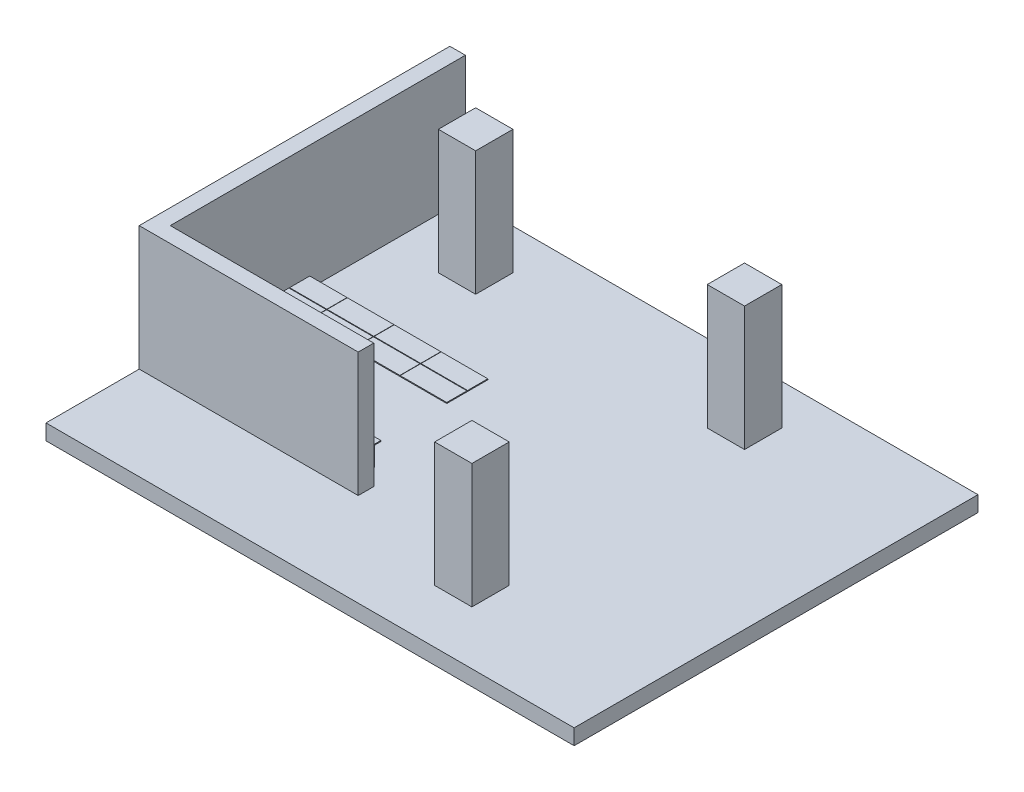
SolidWorks part; units mm, degrees
ref_plane "前视基准面" through (0, 0, 0) normal (0, 0, 1) x (1, 0, 0)
ref_plane "上视基准面" through (0, 0, 0) normal (0, 1, 0) x (1, 0, 0)
ref_plane "右视基准面" through (0, 0, 0) normal (1, 0, 0) x (0, 0, -1)
other "Configuration Table"
sketch "草图2" plane through (0, 0, 0) normal (0, 1, 0) x (1, 0, 0)
  line L5 (0, -500) -> (-500, -500)
  line L6 (0, -500) -> (0, 9500)
  line L7 (0, 9500) -> (-500, 9500)
  line L8 (-500, -500) -> (-500, 9500)
  line L9 (1630, 8200) -> (2830, 8200)
  line L10 (1630, 8200) -> (1630, 7000)
  line L11 (1630, 7000) -> (2830, 7000)
  line L12 (2830, 8200) -> (2830, 7000)
  line L13 (10285, 8200) -> (11485, 8200)
  line L14 (10285, 8200) -> (10285, 7000)
  line L15 (10285, 7000) -> (11485, 7000)
  line L16 (11485, 8200) -> (11485, 7000)
  line L17 (10285, -575) -> (11485, -575)
  line L18 (10285, -575) -> (10285, -1775)
  line L19 (10285, -1775) -> (11485, -1775)
  line L20 (11485, -575) -> (11485, -1775)
  line L21 (0, 0) -> (6550, 0)
  line L22 (0, 0) -> (0, -500)
  line L23 (0, -500) -> (6550, -500)
  line L24 (6550, 0) -> (6550, -500)
  point P4 (8000.3157, 0)
  dimension "D1" = 500
  dimension "D2" = 6550
  dimension "D3" = 500
  dimension "D4" = 10000
  dimension "D5" = 1200
  dimension "D6" = 1630
  dimension "D8" = 7455
  dimension "D9" = 7575
extrude "凸台-拉伸5" add sketch "草图2" along normal blind 4000 contours L6 L7 L8 L5 | L22 L21 L24 L23 | L11 L12 L9 L10 | L15 L16 L13 L14 | L19 L20 L17 L18
sketch "草图3" plane through (0, 0, 0) normal (0, 1, 0) x (1, 0, 0)
  line L1 (-500, 9500) -> (16500, 9500)
  line L2 (-500, 9500) -> (-500, -3500)
  line L3 (-500, -3500) -> (16500, -3500)
  line L4 (16500, 9500) -> (16500, -3500)
  dimension "D1" = 13000
  dimension "D2" = 17000
extrude "凸台-拉伸6" add sketch "草图3" against normal blind 500 contours L3 L4 L1 L2
sketch "草图4" plane through (0, 0, 0) normal (0, 1, 0) x (1, 0, 0)
  line L0 (0, 0) -> (6550, 0) construction
  line L1 (400, 650) -> (1600, 650)
  line L2 (400, 650) -> (400, 0)
  line L3 (400, 0) -> (1600, 0)
  line L4 (1600, 650) -> (1600, 0)
  line L5 (1610, 650) -> (3110, 650)
  line L6 (1610, 650) -> (1610, 0)
  line L7 (1610, 0) -> (3110, 0)
  line L8 (3110, 650) -> (3110, 0)
  line L9 (5905.4419, 3261.9478) -> (5805.4419, 3261.9478)
  line L14 (3120, 650) -> (4620, 650)
  line L19 (0, 0) -> (0, 9500) construction
  line L20 (3120, 650) -> (3120, 0)
  line L21 (3120, 0) -> (4620, 0)
  line L22 (4620, 650) -> (4620, 0)
  line L23 (4630, 650) -> (6130, 650)
  line L24 (4630, 650) -> (4630, 0)
  line L25 (4630, 0) -> (6130, 0)
  line L26 (6130, 650) -> (6130, 0)
  line L27 (1400, 550) -> (1500, 550)
  line L28 (500, 550) -> (600, 550)
  line L29 (500, 550) -> (500, 450)
  line L30 (500, 450) -> (600, 450)
  line L31 (600, 550) -> (600, 450)
  line L32 (500, 200) -> (600, 200)
  line L33 (500, 200) -> (500, 100)
  line L34 (500, 100) -> (600, 100)
  line L35 (600, 200) -> (600, 100)
  line L36 (1710, 550) -> (1810, 550)
  line L37 (1710, 550) -> (1710, 450)
  line L38 (1710, 450) -> (1810, 450)
  line L39 (1810, 550) -> (1810, 450)
  line L40 (1400, 200) -> (1500, 200)
  line L41 (1400, 200) -> (1400, 100)
  line L42 (1400, 100) -> (1500, 100)
  line L43 (1500, 200) -> (1500, 100)
  line L44 (1400, 550) -> (1400, 450)
  line L45 (1400, 450) -> (1500, 450)
  line L46 (1500, 550) -> (1500, 450)
  line L47 (400, 3420) -> (1600, 3420)
  line L48 (1710, 200) -> (1810, 200)
  line L49 (1710, 200) -> (1710, 100)
  line L50 (1710, 100) -> (1810, 100)
  line L51 (1810, 200) -> (1810, 100)
  line L52 (2910, 550) -> (3010, 550)
  line L53 (2910, 550) -> (2910, 450)
  line L54 (2910, 450) -> (3010, 450)
  line L55 (3010, 550) -> (3010, 450)
  line L56 (2910, 200) -> (3010, 200)
  line L57 (2910, 200) -> (2910, 100)
  line L58 (2910, 100) -> (3010, 100)
  line L59 (3010, 200) -> (3010, 100)
  line L60 (3220, 550) -> (3320, 550)
  line L61 (3220, 550) -> (3220, 450)
  line L62 (3220, 450) -> (3320, 450)
  line L63 (3320, 550) -> (3320, 450)
  line L64 (3220, 200) -> (3320, 200)
  line L65 (3220, 200) -> (3220, 100)
  line L66 (3220, 100) -> (3320, 100)
  line L67 (3320, 200) -> (3320, 100)
  line L68 (4420, 550) -> (4520, 550)
  line L69 (4420, 550) -> (4420, 450)
  line L70 (4420, 450) -> (4520, 450)
  line L71 (4520, 550) -> (4520, 450)
  line L72 (4420, 200) -> (4520, 200)
  line L73 (4420, 200) -> (4420, 100)
  line L74 (4420, 100) -> (4520, 100)
  line L75 (4520, 200) -> (4520, 100)
  line L76 (4730, 550) -> (4830, 550)
  line L77 (4730, 550) -> (4730, 450)
  line L78 (4730, 450) -> (4830, 450)
  line L79 (4830, 550) -> (4830, 450)
  line L80 (4730, 200) -> (4830, 200)
  line L81 (4730, 200) -> (4730, 100)
  line L82 (4730, 100) -> (4830, 100)
  line L83 (4830, 200) -> (4830, 100)
  line L84 (5930, 550) -> (6030, 550)
  line L85 (5930, 550) -> (5930, 450)
  line L86 (5930, 450) -> (6030, 450)
  line L87 (6030, 550) -> (6030, 450)
  line L88 (5930, 200) -> (6030, 200)
  line L89 (5930, 200) -> (5930, 100)
  line L90 (5930, 100) -> (6030, 100)
  line L91 (6030, 200) -> (6030, 100)
  line L92 (400, 3420) -> (400, 2770)
  line L93 (400, 2770) -> (1600, 2770)
  line L94 (1600, 3420) -> (1600, 2770)
  line L95 (1610, 2770) -> (3110, 2770)
  line L96 (1610, 2770) -> (1610, 3420)
  line L97 (1610, 3420) -> (3110, 3420)
  line L98 (3110, 2770) -> (3110, 3420)
  line L99 (500, 3990) -> (600, 3990)
  line L100 (3120, 3420) -> (4620, 3420)
  line L101 (3120, 3420) -> (3120, 2770)
  line L102 (3120, 2770) -> (4620, 2770)
  line L103 (4620, 3420) -> (4620, 2770)
  line L104 (4630, 3420) -> (6130, 3420)
  line L105 (4630, 3420) -> (4630, 2770)
  line L106 (4630, 2770) -> (6130, 2770)
  line L107 (6130, 3420) -> (6130, 2770)
  line L108 (400, 4090) -> (1600, 4090)
  line L109 (400, 4090) -> (400, 3440)
  line L110 (400, 3440) -> (1600, 3440)
  line L111 (1600, 4090) -> (1600, 3440)
  line L112 (1610, 4090) -> (3110, 4090)
  line L113 (1610, 4090) -> (1610, 3440)
  line L114 (1610, 3440) -> (3110, 3440)
  line L115 (3110, 4090) -> (3110, 3440)
  line L116 (3120, 4090) -> (4620, 4090)
  line L117 (3120, 4090) -> (3120, 3440)
  line L118 (3120, 3440) -> (4620, 3440)
  line L119 (4620, 4090) -> (4620, 3440)
  line L120 (4630, 4090) -> (6130, 4090)
  line L121 (4630, 4090) -> (4630, 3440)
  line L122 (4630, 3440) -> (6130, 3440)
  line L123 (6130, 4090) -> (6130, 3440)
  line L124 (3675.3992, 7922.7635) -> (4357.151, 7922.7635)
  line L125 (3675.3992, 7922.7635) -> (3675.3992, 7366.5878)
  line L126 (3675.3992, 7366.5878) -> (4357.151, 7366.5878)
  line L127 (4357.151, 7922.7635) -> (4357.151, 7366.5878)
  line L128 (5365.971, 7922.7635) -> (6531.5843, 7922.7635)
  line L129 (5365.971, 7922.7635) -> (5365.971, 7042.152)
  line L130 (5365.971, 7042.152) -> (6531.5843, 7042.152)
  line L131 (6531.5843, 7922.7635) -> (6531.5843, 7042.152)
  line L132 (7643.9357, 7922.7635) -> (8408.6773, 7922.7635)
  line L133 (7643.9357, 7922.7635) -> (7643.9357, 7042.152)
  line L134 (7643.9357, 7042.152) -> (8408.6773, 7042.152)
  line L135 (8408.6773, 7922.7635) -> (8408.6773, 7042.152)
  line L136 (500, 3990) -> (500, 3890)
  line L137 (500, 3890) -> (600, 3890)
  line L138 (600, 3990) -> (600, 3890)
  line L139 (504.367, 3640) -> (604.367, 3640)
  line L140 (504.367, 3640) -> (504.367, 3540)
  line L141 (504.367, 3540) -> (604.367, 3540)
  line L142 (604.367, 3640) -> (604.367, 3540)
  line L143 (1404.367, 3990) -> (1504.367, 3990)
  line L144 (1404.367, 3990) -> (1404.367, 3890)
  line L145 (1404.367, 3890) -> (1504.367, 3890)
  line L146 (1504.367, 3990) -> (1504.367, 3890)
  line L147 (1373.0428, 3640) -> (1473.0428, 3640)
  line L148 (1373.0428, 3640) -> (1373.0428, 3540)
  line L149 (1373.0428, 3540) -> (1473.0428, 3540)
  line L150 (1473.0428, 3640) -> (1473.0428, 3540)
  line L151 (500, 3320) -> (600, 3320)
  line L152 (500, 3320) -> (500, 3220)
  line L153 (500, 3220) -> (600, 3220)
  line L154 (600, 3320) -> (600, 3220)
  line L155 (546.3265, 2970) -> (646.3265, 2970)
  line L156 (546.3265, 2970) -> (546.3265, 2870)
  line L157 (546.3265, 2870) -> (646.3265, 2870)
  line L158 (646.3265, 2970) -> (646.3265, 2870)
  line L159 (1338.9523, 3321.4315) -> (1438.9523, 3321.4315)
  line L160 (1338.9523, 3321.4315) -> (1338.9523, 3221.4315)
  line L161 (1338.9523, 3221.4315) -> (1438.9523, 3221.4315)
  line L162 (1438.9523, 3321.4315) -> (1438.9523, 3221.4315)
  line L163 (1338.9523, 2948.2369) -> (1438.9523, 2948.2369)
  line L164 (1338.9523, 2948.2369) -> (1338.9523, 2848.2369)
  line L165 (1338.9523, 2848.2369) -> (1438.9523, 2848.2369)
  line L166 (1438.9523, 2948.2369) -> (1438.9523, 2848.2369)
  line L167 (1680.1853, 3990) -> (1780.1853, 3990)
  line L168 (1680.1853, 3990) -> (1680.1853, 3890)
  line L169 (1680.1853, 3890) -> (1780.1853, 3890)
  line L170 (1780.1853, 3990) -> (1780.1853, 3890)
  line L171 (1710, 3640) -> (1810, 3640)
  line L172 (1710, 3640) -> (1710, 3540)
  line L173 (1710, 3540) -> (1810, 3540)
  line L174 (1810, 3640) -> (1810, 3540)
  line L175 (1710, 3235.5637) -> (1810, 3235.5637)
  line L176 (1710, 3235.5637) -> (1710, 3135.5637)
  line L177 (1710, 3135.5637) -> (1810, 3135.5637)
  line L178 (1810, 3235.5637) -> (1810, 3135.5637)
  line L179 (1756.7322, 2981.2629) -> (1856.7322, 2981.2629)
  line L180 (1756.7322, 2981.2629) -> (1756.7322, 2881.2629)
  line L181 (1756.7322, 2881.2629) -> (1856.7322, 2881.2629)
  line L182 (1856.7322, 2981.2629) -> (1856.7322, 2881.2629)
  line L183 (2788.7971, 3990) -> (2888.7971, 3990)
  line L184 (2788.7971, 3990) -> (2788.7971, 3890)
  line L185 (2788.7971, 3890) -> (2888.7971, 3890)
  line L186 (2888.7971, 3990) -> (2888.7971, 3890)
  line L187 (2788.7971, 3640) -> (2888.7971, 3640)
  line L188 (2788.7971, 3640) -> (2788.7971, 3540)
  line L189 (2788.7971, 3540) -> (2888.7971, 3540)
  line L190 (2888.7971, 3640) -> (2888.7971, 3540)
  line L191 (2788.7971, 3275.195) -> (2888.7971, 3275.195)
  line L192 (2788.7971, 3275.195) -> (2788.7971, 3175.195)
  line L193 (2788.7971, 3175.195) -> (2888.7971, 3175.195)
  line L194 (2888.7971, 3275.195) -> (2888.7971, 3175.195)
  line L195 (2788.7971, 2981.2629) -> (2888.7971, 2981.2629)
  line L196 (2788.7971, 2981.2629) -> (2788.7971, 2881.2629)
  line L197 (2788.7971, 2881.2629) -> (2888.7971, 2881.2629)
  line L198 (2888.7971, 2981.2629) -> (2888.7971, 2881.2629)
  line L199 (3184.4706, 3990) -> (3284.4706, 3990)
  line L200 (3184.4706, 3990) -> (3184.4706, 3890)
  line L201 (3184.4706, 3890) -> (3284.4706, 3890)
  line L202 (3284.4706, 3990) -> (3284.4706, 3890)
  line L203 (3220, 3640) -> (3320, 3640)
  line L204 (3220, 3640) -> (3220, 3540)
  line L205 (3220, 3540) -> (3320, 3540)
  line L206 (3320, 3640) -> (3320, 3540)
  line L207 (3244.1146, 3235.5637) -> (3344.1146, 3235.5637)
  line L208 (3244.1146, 3235.5637) -> (3244.1146, 3135.5637)
  line L209 (3244.1146, 3135.5637) -> (3344.1146, 3135.5637)
  line L210 (3344.1146, 3235.5637) -> (3344.1146, 3135.5637)
  line L211 (3264.8604, 2981.2629) -> (3364.8604, 2981.2629)
  line L212 (3264.8604, 2981.2629) -> (3264.8604, 2881.2629)
  line L213 (3264.8604, 2881.2629) -> (3364.8604, 2881.2629)
  line L214 (3364.8604, 2981.2629) -> (3364.8604, 2881.2629)
  line L215 (4457.151, 3990) -> (4357.151, 3990)
  line L216 (4457.151, 3990) -> (4457.151, 3890)
  line L217 (4457.151, 3890) -> (4357.151, 3890)
  line L218 (4357.151, 3990) -> (4357.151, 3890)
  line L219 (4291.7753, 3640) -> (4391.7753, 3640)
  line L220 (4291.7753, 3640) -> (4291.7753, 3540)
  line L221 (4291.7753, 3540) -> (4391.7753, 3540)
  line L222 (4391.7753, 3640) -> (4391.7753, 3540)
  line L223 (4245.0974, 3252.6055) -> (4345.0974, 3252.6055)
  line L224 (4245.0974, 3252.6055) -> (4245.0974, 3152.6055)
  line L225 (4245.0974, 3152.6055) -> (4345.0974, 3152.6055)
  line L226 (4345.0974, 3252.6055) -> (4345.0974, 3152.6055)
  line L227 (4291.7753, 2981.2629) -> (4391.7753, 2981.2629)
  line L228 (4291.7753, 2981.2629) -> (4291.7753, 2881.2629)
  line L229 (4291.7753, 2881.2629) -> (4391.7753, 2881.2629)
  line L230 (4391.7753, 2981.2629) -> (4391.7753, 2881.2629)
  line L231 (4663.3016, 3305.1829) -> (4763.3016, 3305.1829)
  line L232 (4663.3016, 3305.1829) -> (4663.3016, 3205.1829)
  line L233 (4663.3016, 3205.1829) -> (4763.3016, 3205.1829)
  line L234 (4763.3016, 3305.1829) -> (4763.3016, 3205.1829)
  line L235 (4711.2762, 2923.2666) -> (4811.2762, 2923.2666)
  line L236 (4711.2762, 2923.2666) -> (4711.2762, 2823.2666)
  line L237 (4711.2762, 2823.2666) -> (4811.2762, 2823.2666)
  line L238 (4811.2762, 2923.2666) -> (4811.2762, 2823.2666)
  line L239 (4693.7244, 3540) -> (4793.7244, 3540)
  line L240 (4693.7244, 3540) -> (4693.7244, 3640)
  line L241 (4693.7244, 3640) -> (4793.7244, 3640)
  line L242 (4793.7244, 3540) -> (4793.7244, 3640)
  line L243 (4693.7244, 3990) -> (4793.7244, 3990)
  line L244 (4693.7244, 3990) -> (4693.7244, 3890)
  line L245 (4693.7244, 3890) -> (4793.7244, 3890)
  line L246 (4793.7244, 3990) -> (4793.7244, 3890)
  line L247 (5993.6857, 3990) -> (5893.6857, 3990)
  line L248 (5993.6857, 3990) -> (5993.6857, 3890)
  line L249 (5993.6857, 3890) -> (5893.6857, 3890)
  line L250 (5893.6857, 3990) -> (5893.6857, 3890)
  line L251 (5806.8633, 3640) -> (5906.8633, 3640)
  line L252 (5806.8633, 3640) -> (5806.8633, 3540)
  line L253 (5806.8633, 3540) -> (5906.8633, 3540)
  line L254 (5906.8633, 3640) -> (5906.8633, 3540)
  line L255 (5897.8822, 3023.5868) -> (5797.8822, 3023.5868)
  line L256 (5897.8822, 3023.5868) -> (5897.8822, 2923.5868)
  line L257 (5897.8822, 2923.5868) -> (5797.8822, 2923.5868)
  line L258 (5797.8822, 3023.5868) -> (5797.8822, 2923.5868)
  line L259 (5905.4419, 3261.9478) -> (5905.4419, 3161.9478)
  line L260 (5905.4419, 3161.9478) -> (5805.4419, 3161.9478)
  line L261 (5805.4419, 3261.9478) -> (5805.4419, 3161.9478)
  dimension "D1" = 650
  dimension "D2" = 1200
  dimension "D3" = 10
  dimension "D4" = 1500
  dimension "D5" = 10
  dimension "D6" = 10
  dimension "D7" = 400
  dimension "D8" = 100
  dimension "D9" = 100
  dimension "D10" = 100
  dimension "D11" = 100
  dimension "D12" = 100
  dimension "D13" = 100
  dimension "D14" = 100
  dimension "D15" = 100
  dimension "D16" = 100
  dimension "D17" = 100
  dimension "D18" = 100
  dimension "D19" = 100
  dimension "D20" = 100
  dimension "D21" = 100
  dimension "D22" = 100
  dimension "D23" = 100
  dimension "D24" = 100
  dimension "D25" = 100
  dimension "D26" = 100
  dimension "D27" = 2120
  dimension "D28" = 20
  dimension "D29" = 10
  dimension "D30" = 10
  dimension "D31" = 10
  dimension "D32" = 10
  dimension "D33" = 10
  dimension "D34" = 10
  dimension "D35" = 100
  dimension "D36" = 100
  dimension "D37" = 100
  dimension "D38" = 100
  dimension "D39" = 100
extrude "凸台-拉伸7" add sketch "草图4" against normal blind 30 from offset 750 contours L23 L26 L25 L24 | L14 L22 L21 L20 | L5 L8 L7 L6 | L1 L4 L3 L2 | L93 L94 L47 L92 | L108 L111 L110 L109 | L112 L115 L114 L113 | L95 L98 L97 L96 | L102 L103 L100 L101 | L106 L107 L104 L105 | L116 L119 L118 L117 | L120 L123 L122 L121
extrude "凸台-拉伸8" add sketch "草图4<3>" along normal up to surface (720 mm away) contours L88 L91 L90 L89 | L86 L87 L84 L85 | L80 L83 L82 L81 | L78 L79 L76 L77 | L72 L75 L74 L73 | L70 L71 L68 L69 | L64 L67 L66 L65 | L62 L63 L60 L61 | L56 L59 L58 L57 | L54 L55 L52 L53 | L48 L51 L50 L49 | L36 L39 L38 L37 | L40 L43 L42 L41 | L45 L46 L27 L44 | L32 L35 L34 L33 | L30 L31 L28 L29 up to face at (2360, 720, -325)
sketch "草图4<3>" plane through (0, 0, 0) normal (0, 1, 0) x (1, 0, 0) same geometry as "草图4"
